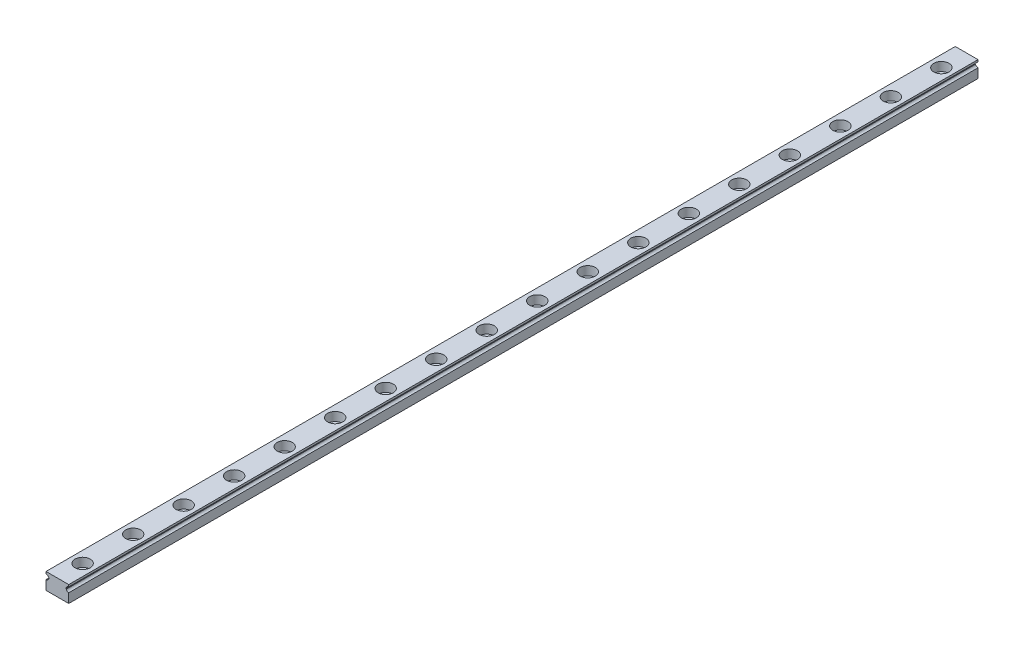
SolidWorks part; units mm, degrees
ref_plane "Спереди" through (0, 0, 0) normal (0, 0, 1) x (1, 0, 0)
ref_plane "Сверху" through (0, 0, 0) normal (0, 1, 0) x (1, 0, 0)
ref_plane "Справа" through (0, 0, 0) normal (1, 0, 0) x (0, 0, -1)
sketch "Sketch1" plane through (0, 0, 0) normal (0, 0, 1) x (1, 0, 0)
  line L0 (0, 0) -> (0, 5.7299) construction
  line L1 (-4.5, -3.25) -> (4.5, -3.25)
  line L2 (-4.5, -3.25) -> (-4.5, 0.45)
  line L3 (-4.5, 3.25) -> (4.5, 3.25)
  line L4 (4.5, -3.25) -> (4.5, 0.45)
  line L5 (-4.5, -3.25) -> (4.5, 3.25) construction
  line L6 (-4.5, 3.25) -> (4.5, -3.25) construction
  line L7 (-4.5, 2.45) -> (-4.5, 3.25)
  line L8 (-3.5318, 1.2) -> (-3.4, 1.2)
  line L9 (3.5318, 1.2) -> (3.4, 1.2)
  line L10 (-3.5318, 1.7) -> (-3.4, 1.7)
  line L11 (-3.4, 1.2) -> (-3.4, 1.7)
  line L12 (3.4, 1.2) -> (3.4, 1.7)
  line L13 (3.5318, 1.7) -> (3.4, 1.7)
  line L14 (4.5, 2.45) -> (4.5, 3.25)
  line L15 (-3.4, 1.45) -> (-4.5, 1.45) construction
  arc A0 (-3.5318, 1.7) -> (-4.5, 2.45) centre (-4.5, 1.45) ccw
  arc A1 (-4.5, 0.45) -> (-3.5318, 1.2) centre (-4.5, 1.45) ccw
  arc A2 (4.5, 0.45) -> (3.5318, 1.2) centre (4.5, 1.45) cw
  arc A3 (3.5318, 1.7) -> (4.5, 2.45) centre (4.5, 1.45) cw
  point P0 (0, 0)
  dimension "D3" = 1
  dimension "D1" = 9
  dimension "D2" = 6.5
  dimension "D4" = 2.05
  dimension "D5" = 6.8
  dimension "D6" = 0.5
extrude "Extrude1" add sketch "Sketch1" along normal blind 360
sketch "Sketch2" plane through (0, 3.25, 0) normal (0, 1, 0) x (1, 0, 0)
  line L0 (4.5, 0) -> (-4.5, 0) construction
  circle A0 centre (0, -10) radius 1.75
  circle A1 centre (0, -10) radius 3
  dimension "D1" = 3.5
  dimension "D2" = 6
  dimension "D3" = 10
extrude "Extrude2" cut sketch "Sketch2" against normal blind 3.5 contours A1
extrude "Extrude3" cut sketch "Sketch" against normal through all contours A0
sketch "Sketch" plane through (0, 3.25, 0) normal (0, 1, 0) x (1, 0, 0) same geometry as "Sketch2"
pattern_linear "LPattern1" count 40 spacing 20 along (0, 0, 1) of "Extrude2", "Extrude3"
chamfer "Chamfer1" [suppressed] distance 0.3 angle 45
